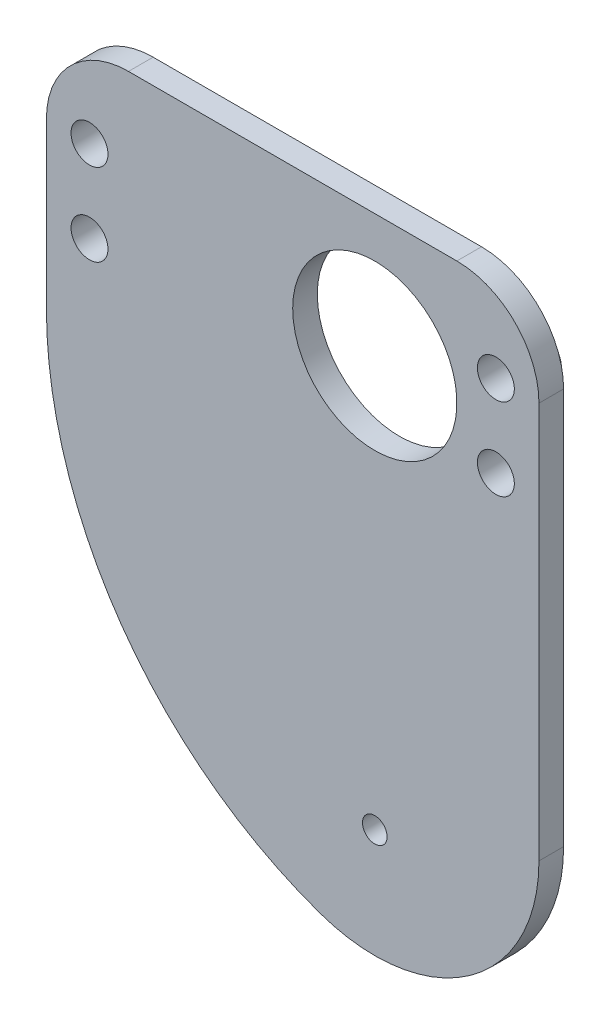
SolidWorks part; units mm, degrees
ref_plane "前视基准面" through (0, 0, 0) normal (0, 0, 1) x (1, 0, 0)
ref_plane "上视基准面" through (0, 0, 0) normal (0, 1, 0) x (1, 0, 0)
ref_plane "右视基准面" through (0, 0, 0) normal (1, 0, 0) x (0, 0, -1)
sketch "草图3" plane through (0, 0, 0) normal (0, 0, 1) x (1, 0, 0)
  line L0 (60.2665, 6.5325) -> (60.2665, 16.5325)
  line L1 (10.7665, 16.5325) -> (10.7665, 6.5325)
  line L2 (10.7665, 16.5325) -> (60.2665, 16.5325)
  circle A0 centre (60.2665, 16.5325) radius 3
  circle A1 centre (60.2665, 6.5325) radius 3
  circle A6 centre (10.7665, 6.5325) radius 3
  circle A7 centre (10.7665, 16.5325) radius 3
  dimension "D1" = 6
  dimension "D2" = 6
  dimension "D4" = 6
  dimension "D5" = 6
  dimension "D3" = 10
  dimension "D6" = 49.5
  dimension "D7" = 49.5
  dimension "D8" = 10
extrude "凸台-拉伸6" add sketch "草图3" along normal blind 2 contours A6 | A0 | A1 | A7
sketch "草图11" plane through (0, 0, 2) normal (0, 0, 1) x (1, 0, 0)
  circle A0 centre (10.7665, 16.5325) radius 2.25
  circle A1 centre (10.7665, 6.5325) radius 2.25
  circle A2 centre (60.2665, 16.5325) radius 2.25
  circle A3 centre (60.2665, 6.5325) radius 2.25
  dimension "D1" = 4.5
  dimension "D2" = 4.5
  dimension "D3" = 4.5
  dimension "D4" = 4.5
extrude "切除-拉伸2" cut sketch "草图11" against normal blind 2 and the other way blind 10
sketch "草图12" plane through (0, 0, 2) normal (0, 0, 1) x (1, 0, 0)
  line L4 (10.7665, 16.5325) -> (60.2665, 6.5325) construction
  line L5 (10.7665, 6.5325) -> (60.2665, 16.5325) construction
  line L6 (60.2665, 16.5325) -> (60.2665, 6.5325) construction
  line L7 (5.5165, 26.5325) -> (65.5165, 26.5325)
  line L8 (5.5165, 26.5325) -> (5.5165, -53.4675)
  line L9 (5.5165, -53.4675) -> (65.5165, -53.4675)
  line L10 (65.5165, 26.5325) -> (65.5165, -53.4675)
  circle A4 centre (45.5165, 11.5325) radius 10
  point P8 (35.5165, 11.5325)
  point P9 (35.5165, 26.5325)
  point P10 (-46.6091, 14.6442)
  point P11 (60.2665, 11.5325)
  dimension "D5" = 20
  dimension "D1" = 60
  dimension "D2" = 80
  dimension "D3" = 15
  dimension "D4" = 14.75
extrude "凸台-拉伸7" add sketch "草图12" along normal blind 3 contours L7 L10 L9 L8
sketch "草图14" plane through (0, 0, 2) normal (0, 0, -1) x (-1, 0, 0)
  line L0 (-60.2665, 16.5325) -> (-60.2665, 6.5325) construction
  circle A0 centre (-60.2665, 6.5325) radius 2.25 construction
  circle A1 centre (-60.2665, 6.5325) radius 2.25
  circle A2 centre (-60.2665, 16.5325) radius 2.25 construction
  circle A3 centre (-60.2665, 16.5325) radius 2.25
  circle A4 centre (-10.7665, 6.5325) radius 2.25 construction
  circle A5 centre (-10.7665, 16.5325) radius 2.25 construction
  circle A6 centre (-10.7665, 6.5325) radius 2.25
  circle A7 centre (-10.7665, 16.5325) radius 2.25
  circle A8 centre (-45.5165, 11.5325) radius 10
  point P14 (-60.2665, 11.5325)
  point P15 (0.1696, -0.033)
  dimension "D2" = 20
  dimension "D1" = 14.75
extrude "切除-拉伸3" cut sketch "草图14" against normal blind 3
sketch "草图15" plane through (0, 0, 2) normal (0, 0, -1) x (-1, 0, 0)
  circle A0 centre (-45.5165, 11.5325) radius 10 construction
  circle A1 centre (-45.5165, 11.5325) radius 10
  circle A2 centre (-45.5165, -38.4675) radius 1.5
  dimension "D2" = 3
  dimension "D1" = 50
extrude "切除-拉伸4" cut sketch "草图15" against normal blind 3
fillet "圆角2" radius 50 1 edges at (5.5165, -53.4675, 3.5)
fillet "圆角3" radius 20 1 edges at (65.5165, -53.4675, 3.5)
fillet "圆角4" radius 10 2 edges at (65.5165, 26.5325, 3.5) (5.5165, 26.5325, 3.5)
